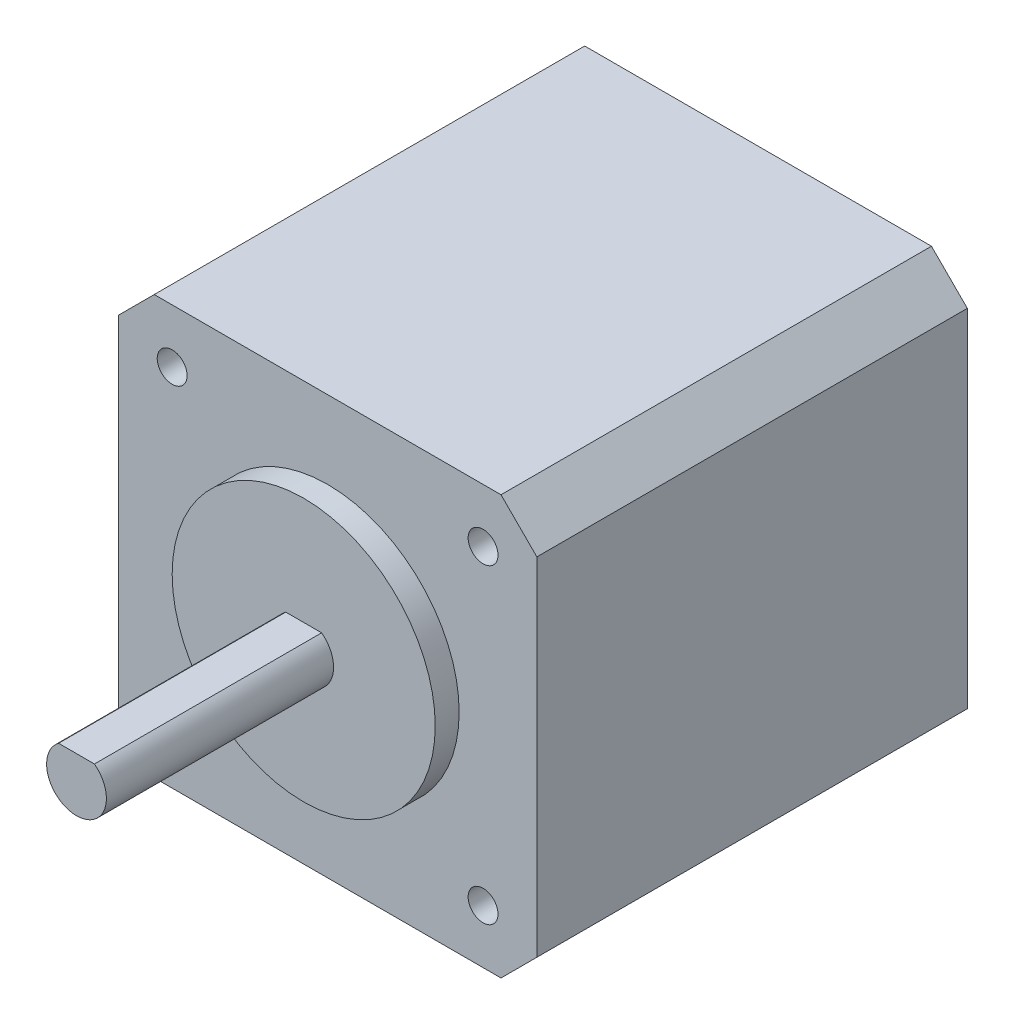
SolidWorks part; units mm, degrees
ref_plane "Front Plane" through (0, 0, 0) normal (0, 0, 1) x (1, 0, 0)
ref_plane "Top Plane" through (0, 0, 0) normal (0, 1, 0) x (1, 0, 0)
ref_plane "Right Plane" through (0, 0, 0) normal (1, 0, 0) x (0, 0, -1)
sketch "Sketch1" plane through (0, 0, 0) normal (0, 0, 1) x (1, 0, 0)
  line L0 (-14.5, 17.5) -> (-17.5, 14.5)
  line L1 (14.5, -17.5) -> (-14.5, -17.5)
  line L2 (17.5, -14.5) -> (17.5, 14.5)
  line L3 (14.5, 17.5) -> (-14.5, 17.5)
  line L4 (-17.5, -14.5) -> (-17.5, 14.5)
  line L5 (17.5, -17.5) -> (-17.5, 17.5) construction
  line L6 (17.5, 17.5) -> (-17.5, -17.5) construction
  line L7 (17.5, 14.5) -> (14.5, 17.5)
  line L8 (17.5, -14.5) -> (14.5, -17.5)
  line L9 (-14.5, -17.5) -> (-17.5, -14.5)
  line L10 (-1.5, 2) -> (1.5, 2)
  arc A0 (-1.5, 2) -> (1.5, 2) centre (0, 0) ccw
  circle A1 centre (0, 0) radius 11
  arc A2 (-1.5, 2) -> (1.5, 2) centre (0, 0) cw construction
  point P0 (0, 0)
  point P6 (-13, 13)
  point P12 (13, 13)
  point P13 (13, -13)
  point P14 (-13, -13)
  point P15 (0, 0)
  point P24 (0, 2.5)
  dimension "D2" = 22
  dimension "D3" = 4
  dimension "D5" = 5
  dimension "D1" = 35
  dimension "D4" = 26
  dimension "D6" = 0.5
extrude "Boss-Extrude1" add sketch "Sketch1" against normal blind 36 contours L3 L0 L4 L9 L1 L8 L2 L7
extrude "Boss-Extrude2" add sketch "Sketch1<3>" along normal blind 2 contours A1
sketch "Sketch1<3>" plane through (0, 0, 0) normal (0, 0, 1) x (1, 0, 0) same geometry as "Sketch1"
hole_wizard "M3x0.5 Tapped Hole1" positions "Sketch3" profile "Sketch2" tap size "M3x0.5" standard "ANSI Metric"
sketch "Sketch3" plane through (0, 0, 0) normal (0, 0, 1) x (1, 0, 0)
  point P0 (13, 13)
  point P3 (-13, 13)
  point P6 (-13, -13)
  point P9 (13, -13)
sketch "Sketch2" plane through (13, 13, 0) normal (1, 0, 0) x (0, -1, 0)
  line L0 (0, 0) -> (0, 5.7511)
  line L1 (0, 5.7511) -> (1.25, 5)
  line L2 (1.25, 5) -> (1.25, 0)
  line L5 (1.25, 0) -> (0, 0)
  line L10 (0, 5.7511) -> (-1.25, 5) construction
  line L11 (0, -6.35) -> (0, 107.95) construction
  dimension "Tap Drill Dia." = 2.5
  dimension "Tap Drill Depth" = 5
  dimension "Drill Angle" = 118
cosmetic thread "Hole Thread1"
cosmetic thread "Hole Thread2"
cosmetic thread "Hole Thread3"
cosmetic thread "Hole Thread4"
extrude "Boss-Extrude3" add sketch "Sketch1<4>" along normal blind 21 contours L10 A0 region at (0, -0.1209, 0)
sketch "Sketch1<4>" plane through (0, 0, 0) normal (0, 0, 1) x (1, 0, 0) same geometry as "Sketch1"
